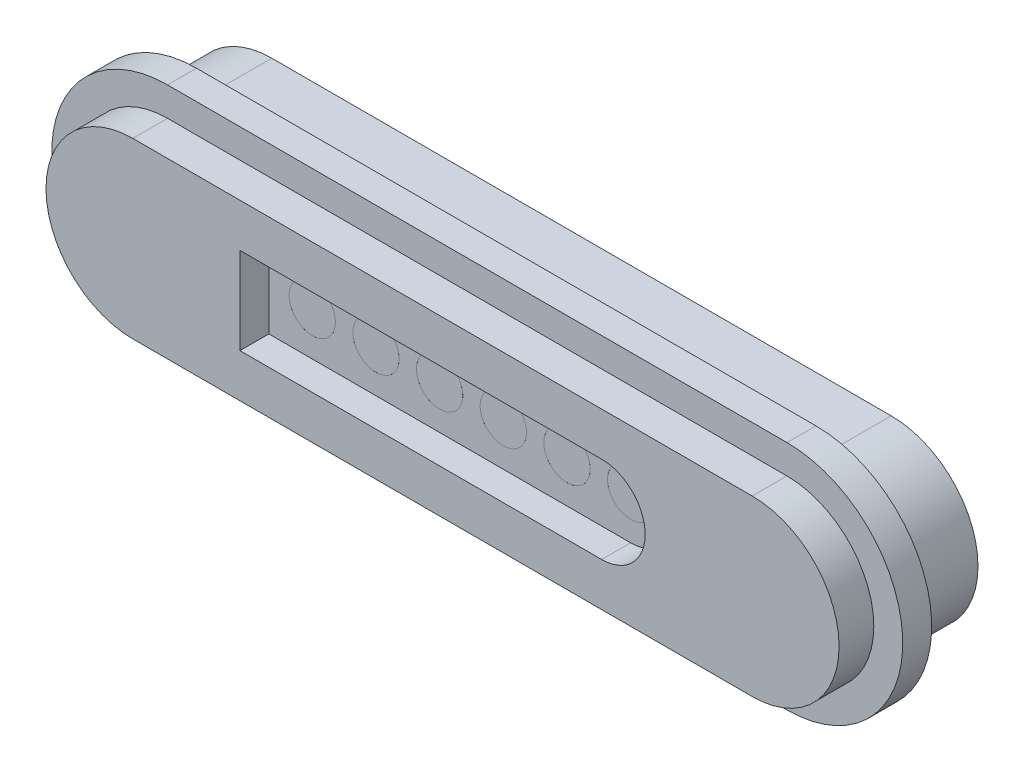
SolidWorks part; units mm, degrees
ref_plane "Front Plane" through (0, 0, 0) normal (0, 0, 1) x (1, 0, 0)
ref_plane "Top Plane" through (0, 0, 0) normal (0, 1, 0) x (1, 0, 0)
ref_plane "Right Plane" through (0, 0, 0) normal (1, 0, 0) x (0, 0, -1)
sketch "Sketch1" plane through (0, 0, 0) normal (0, 0, 1) x (1, 0, 0)
  line L0 (-10.3156, -0.6603) -> (11.0844, -0.6603) construction
  line L1 (-10.3156, 3.3397) -> (11.0844, 3.3397)
  line L2 (-10.3156, -4.6603) -> (11.0844, -4.6603)
  line L3 (-10.3156, -0.6603) -> (11.0844, -0.6603) construction
  line L4 (-10.3156, 2.3397) -> (11.0844, 2.3397)
  line L5 (-10.3156, -3.6603) -> (11.0844, -3.6603)
  line L6 (0.3844, -0.6603) -> (0.3844, 5.2369) construction
  line L7 (6.6712, -2.0074) -> (-6.6156, 0.8396) construction
  line L8 (6.6712, 0.6868) -> (-6.6156, -2.1603) construction
  line L9 (5.8844, -2.1603) -> (-6.6156, -2.1603)
  line L10 (-6.6156, 0.8396) -> (5.8983, 0.8396)
  line L11 (-6.6156, -2.1603) -> (-6.6156, 0.8396)
  arc A0 (-10.3156, 3.3397) -> (-10.3156, -4.6603) centre (-10.3156, -0.6603) ccw
  arc A1 (11.0844, -4.6603) -> (11.0844, 3.3397) centre (11.0844, -0.6603) ccw
  arc A2 (-10.3156, 2.3397) -> (-10.3156, -3.6603) centre (-10.3156, -0.6603) ccw
  arc A3 (11.0844, -3.6603) -> (11.0844, 2.3397) centre (11.0844, -0.6603) ccw
  circle A4 centre (1.4844, -0.6603) radius 0.8
  circle A5 centre (3.6844, -0.6603) radius 0.8
  circle A6 centre (5.8844, -0.6603) radius 0.8
  circle A7 centre (-5.1156, -0.6603) radius 0.8
  circle A8 centre (-2.9156, -0.6603) radius 0.8
  circle A9 centre (-0.7156, -0.6603) radius 0.8
  arc A10 (5.8983, 0.8396) -> (5.8844, -2.1603) centre (5.8844, -0.6603) cw
  point P2 (0.3844, -0.6603)
  point P11 (0.3844, -0.6603)
  point P36 (7.3844, -0.6673)
  dimension "D5" = 1.6
  dimension "D6" = 1.6
  dimension "D7" = 1.6
  dimension "D1" = 6
  dimension "D2" = 2.2
  dimension "D3" = 2.2
  dimension "D4" = 1.1
  dimension "D8" = 14
extrude "Boss-Extrude1" add sketch "Sketch1" along normal blind 4.8 contours L5 A3 L4 A2 L10 A10 L9 L11 region at (0.3844, 2.0592, 0)
extrude "Boss-Extrude2" add sketch "Sketch1<3>" along normal blind 3.8 contours A10 L10 L11 L9 A8 A4 A5 A6 A7 A9 region at (0.1622, -0.6604, 0)
sketch "Sketch1<3>" plane through (0, 0, 0) normal (0, 0, 1) x (1, 0, 0) same geometry as "Sketch1"
extrude "Boss-Extrude3" add sketch "Sketch1<4>" along normal blind 1 from offset 2.6 contours L2 A1 L1 A0 A3 L5 A2 L4 region at (0.3844, 3.035, 0)
sketch "Sketch1<4>" plane through (0, 0, 0) normal (0, 0, 1) x (1, 0, 0) same geometry as "Sketch1"
extrude "Boss-Extrude4" add sketch "Sketch1<5>" along normal blind 3.8 and the other way blind 1.5 separate body contours A6 | A5 | A4 | A9 | A8 | A7 region at (1.4844, -0.6603, 0) region at (3.6844, -0.6603, 0) region at (5.8844, -0.6603, 0) region at (-5.1156, -0.6603, 0) region at (-2.9156, -0.6603, 0) region at (-0.7156, -0.6603, 0)
sketch "Sketch1<5>" plane through (0, 0, 0) normal (0, 0, 1) x (1, 0, 0) same geometry as "Sketch1"
